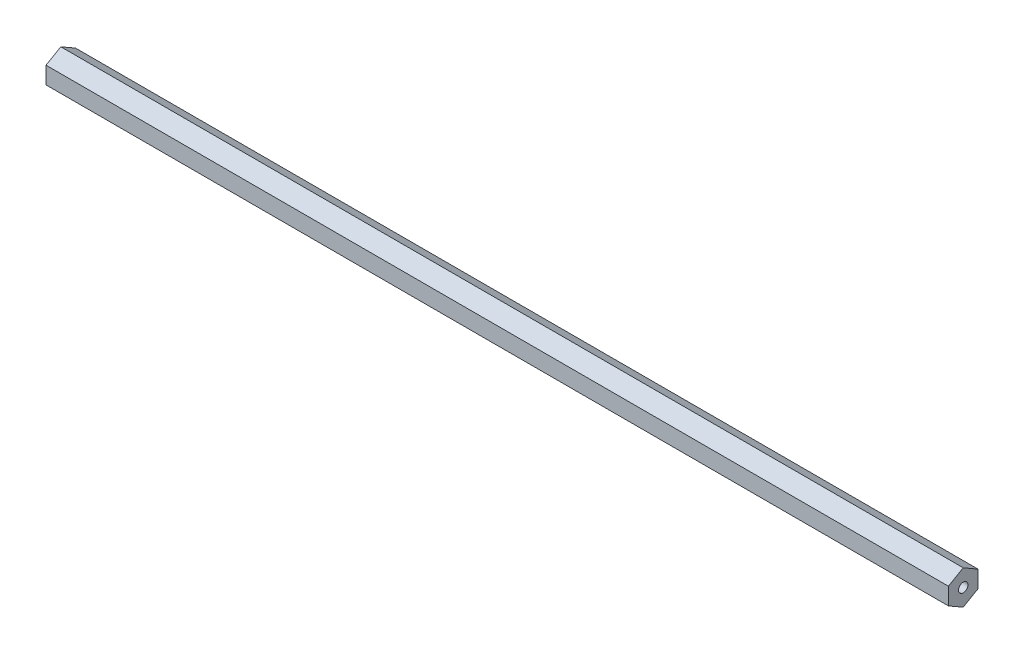
SolidWorks part; units mm, degrees
material "7075-T6 (SN)"
ref_plane "Front Plane" through (0, 0, 0) normal (0, 0, 1) x (1, 0, 0)
ref_plane "Top Plane" through (0, 0, 0) normal (0, 1, 0) x (1, 0, 0)
ref_plane "Right Plane" through (0, 0, 0) normal (1, 0, 0) x (0, 0, -1)
sketch "Sketch1" plane through (0, 0, 0) normal (1, 0, 0) x (0, 0, -1)
  line L1 (0, 7.3323) -> (-6.35, 3.6662)
  line L2 (-6.35, 3.6662) -> (-6.35, -3.6662)
  line L3 (-6.35, -3.6662) -> (0, -7.3323)
  line L4 (0, -7.3323) -> (6.35, -3.6662)
  line L5 (6.35, -3.6662) -> (6.35, 3.6662)
  line L6 (6.35, 3.6662) -> (0, 7.3323)
  circle A1 centre (0, 0) radius 6.35
  circle A2 centre (0, 0) radius 6.35 construction
  dimension "D1" = 12.7
  dimension "D2" = 12.7
extrude "Boss-Extrude1" add sketch "Sketch1" along normal mid plane 387.2865 contours A1 | A1 L1 L2 | L6 L1 L2 L3 L4 L5 region at (0, 3.2816, 5.6838) region at (0, 0, 0)
hole_wizard "#10-32 Tapped Hole1" positions "3DSketch1" profile "Sketch2" tap size "#10-32" standard "ANSI Inch"
sketch3d "3DSketch1"
  line L0 (177.8, 0, 0) -> (-177.8, 0, 0) construction
  point P0 (193.6432, 0, 0)
  point P7 (-193.6433, 0, 0)
sketch "Sketch2" plane through (193.6432, 0, 0) normal (0, 1, 0) x (0, 0, -1)
  line L0 (0, 0) -> (0, 13.2428)
  line L1 (0, 13.2428) -> (2.0193, 12.0294)
  line L2 (2.0193, 12.0294) -> (2.0193, 0)
  line L5 (2.0193, 0) -> (0, 0)
  line L10 (0, 13.2428) -> (-2.0193, 12.0294) construction
  line L11 (0, -6.35) -> (0, 107.95) construction
  dimension "Tap Drill Dia." = 4.0386
  dimension "Tap Drill Depth" = 12.0294
  dimension "Drill Angle" = 118
cosmetic thread "Hole Thread1"
cosmetic thread "Hole Thread2"
